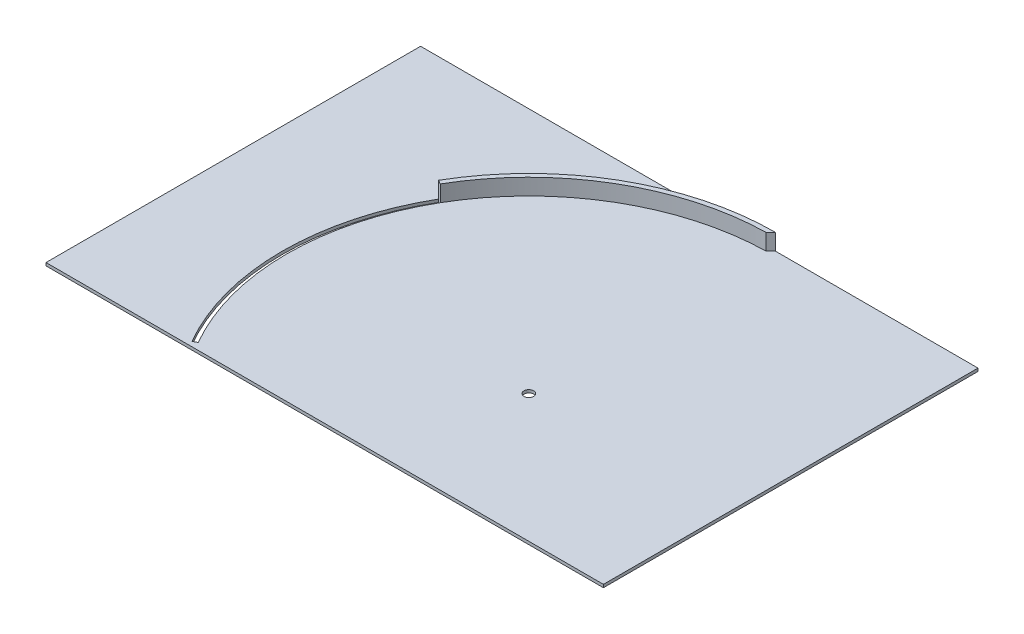
SolidWorks part; units mm, degrees
ref_plane "Front Plane" through (0, 0, 0) normal (0, 0, 1) x (1, 0, 0)
ref_plane "Top Plane" through (0, 0, 0) normal (0, 1, 0) x (1, 0, 0)
ref_plane "Right Plane" through (0, 0, 0) normal (1, 0, 0) x (0, 0, -1)
sketch "Sketch3" plane through (0, 0, 0) normal (0, 1, 0) x (1, 0, 0)
  line L1 (0, 0) -> (-839.8654, 0) construction
  line L2 (0, 0) -> (-451.1992, 260.5) construction
  line L3 (0, 531) -> (0, 521)
  line L4 (-459.8595, 265.5) -> (-451.1992, 260.5)
  circle A0 centre (0, 0) radius 250 construction
  arc A1 (0, 521) -> (-451.1992, 260.5) centre (0, 0) ccw
  arc A2 (0, 531) -> (-459.8595, 265.5) centre (0, 0) ccw
  dimension "D1" = 500
  dimension "D2" = 521
  dimension "D3" = 30
  dimension "D4" = 10
extrude "Boss-Extrude1" add sketch "Sketch3" along normal blind 35
sketch "Sketch4" plane through (0, 0, 0) normal (0, 1, 0) x (1, 0, 0)
  line L1 (-764.07, -275.4) -> (435.93, -275.4)
  line L2 (-764.07, -275.4) -> (-764.07, 531)
  line L3 (-764.07, 531) -> (435.93, 531)
  line L4 (435.93, -275.4) -> (435.93, 531)
  arc A0 (0, 531) -> (-459.8595, 265.5) centre (0, 0) ccw construction
  dimension "D1" = 1200
  dimension "D2" = 275.4
  dimension "D3" = 764.07
extrude "Boss-Extrude2" add sketch "Sketch4" against normal blind 6.35
chamfer "Chamfer1" distance 10 angle 45 1 edges at (0, 17.5, -521)
hole_wizard "Ø20.0mm Dowel Hole1" positions "Sketch6" profile "Sketch7" hole size "Ø20.0" standard "ANSI Metric" end condition through all
sketch "Sketch6" plane through (0, 0, 0) normal (0, 1, 0) x (1, 0, 0)
  point P0 (0, 0)
sketch "Sketch7" plane through (0, 0, 0) normal (1, 0, 0) x (0, 0, 1)
  line L0 (0, 0) -> (0, 6.35)
  line L1 (0, 6.35) -> (10.5, 6.35)
  line L2 (10.5, 6.35) -> (10.5, 0)
  line L5 (10.5, 0) -> (0, 0)
  line L11 (0, -6.35) -> (0, 107.95) construction
  dimension "Thru Hole Dia." = 21
  dimension "Thru Hole Depth" = 6.35
sketch "Sketch8" plane through (0, 0, 0) normal (0, 1, 0) x (1, 0, 0)
  line L0 (-451.1992, 260.5) -> (-459.8595, 265.5)
  line L1 (-451.1992, -260.5) -> (-459.8595, -265.5)
  arc A0 (-451.1992, 260.5) -> (-451.1992, -260.5) centre (0, 0) ccw
  arc A1 (-459.8595, 265.5) -> (-459.8595, -265.5) centre (0, 0) ccw
  point P3 (0, 0)
  dimension "D1" = 10
extrude "Cut-Extrude1" cut sketch "Sketch8" against normal through all
equation "\"D2@Sketch3\"=(\"D1@Sketch3\"/2)+271"
